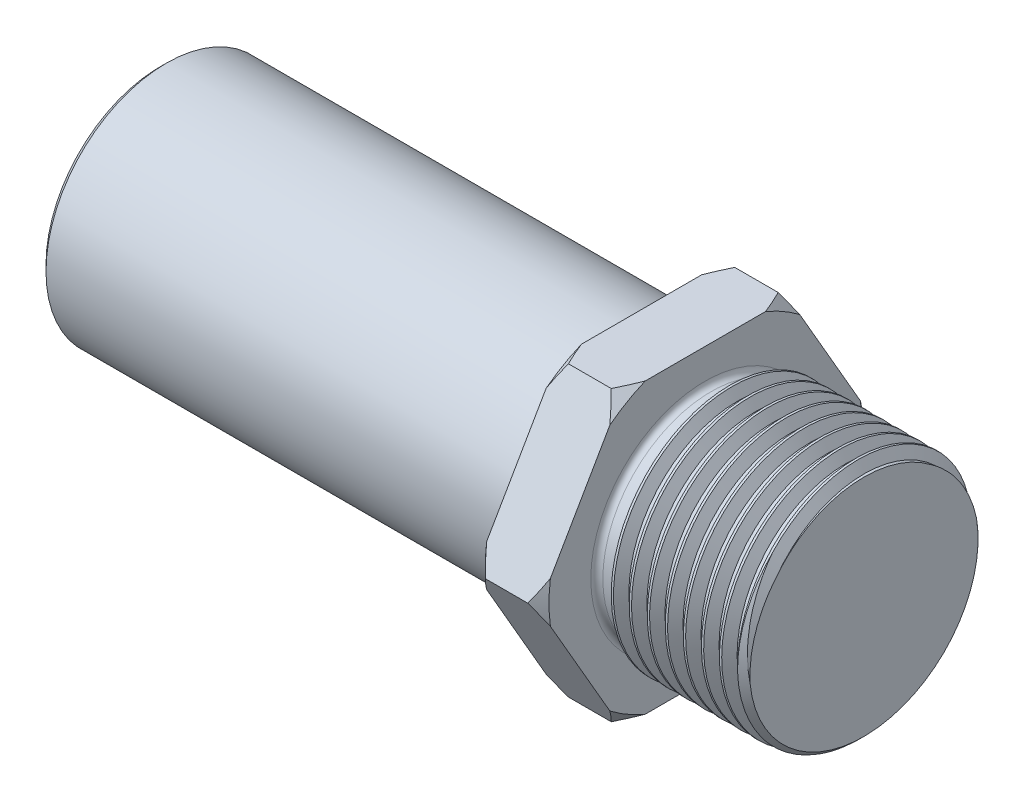
SolidWorks part; units mm, degrees
material "AISI 1045 Acero estirado en frío"
ref_plane "Alzado" through (0, 0, 0) normal (0, 0, 1) x (1, 0, 0)
ref_plane "Planta" through (0, 0, 0) normal (0, 1, 0) x (1, 0, 0)
ref_plane "Vista lateral" through (0, 0, 0) normal (1, 0, 0) x (0, 0, -1)
sketch "Croquis1" plane through (0, 0, 0) normal (0, 1, 0) x (1, 0, 0)
  line L0 (0, 0) -> (-85.2, 0) construction
  line L1 (0, 0) -> (0, 10)
  line L6 (0, 10) -> (-84.992, 10)
  line L7 (-85.2, 10) -> (-85.2, 0)
  line L8 (0, 0) -> (-85.2, 0)
  line L14 (-84.992, 10) -> (-85.2, 10)
  dimension "D3" = 20
revolve "Revolución1" add sketch "Croquis1" angle 360 about L0
sketch "Croquis2" plane through (0, 0, 0) normal (1, 0, 0) x (0, 0, -1)
  circle A1 centre (0, 0) radius 10
  circle A3 centre (0, 0) radius 10
  dimension "D1" = 0
extrude "Cortar-Extruir1" cut sketch "Croquis2" against normal blind 23
chamfer "Chaflán1" distance 0.6 angle 45 1 edges at (-85.2, 0, -10)
sketch "Croquis3" plane through (-23, 0, 0) normal (1, 0, 0) x (0, 0, -1)
  circle A1 centre (0, 0) radius 10
  circle A3 centre (0, 0) radius 10
  dimension "D1" = 0
extrude "Saliente-Extruir1" add sketch "Croquis3" along normal blind 8
sketch "Croquis4" plane through (-85.2, 0, 0) normal (-1, 0, 0) x (0, 0, 1)
  circle A0 centre (0, 0) radius 17.8458
extrude "Cortar-Extruir2" cut sketch "Croquis4" against normal blind 11.7
hole_wizard "Perforador para roscar para macho de roscar para M16x1.51" positions "Croquis5" profile "Croquis7" hole size "M16x1.5" standard "Ansi Metric"
sketch "Croquis5" plane through (-73.5, 0, 0) normal (-1, 0, 0) x (0, 0, 1)
  point P0 (0, 0)
sketch "Croquis7" plane through (-73.5, 0, 0) normal (0, 1, 0) x (0, 0, 1)
  line L0 (0, 0) -> (0, 19.3562)
  line L1 (0, 19.3562) -> (7.25, 15)
  line L2 (7.25, 15) -> (7.25, 0)
  line L5 (7.25, 0) -> (0, 0)
  line L10 (0, 19.3562) -> (-7.25, 15) construction
  line L11 (0, -6.35) -> (0, 107.95) construction
  dimension "Diámetro de taladro" = 14.5
  dimension "Profundidad de taladro" = 15
  dimension "Ángulo de perforador" = 118
thread "Rosca2" pitch 1.5 method cut profile "Perfil de rosca2" start angle 0, offset 0, length 14, pitch 1.5, diameter 14.5
ref_plane "Plano2" through (-73.5, 0, -7.25) normal (0, -1, 0) x (0, 0, -1)
sketch "Perfil de rosca2" plane through (-73.5, 0, -7.25) normal (0, -1, 0) x (0, 0, -1)
  line L0 (0, 0) -> (0, 1.5) construction
  line L1 (0, 0) -> (0.8119, 0.4687)
  line L2 (0.8119, 0.4687) -> (0.8119, 0.6562)
  line L3 (0.8119, 0.6562) -> (0, 1.125)
  line L4 (0.8119, 0.5625) -> (0, 0.5625) construction
  line L11 (0, 0) -> (0, 1.125)
  point P2 (0, 0)
  dimension "Pitch" = 1.5
  dimension "Profile_Angle" = 60
  dimension "Profile_Land" = 0.1875
  dimension "Profile_Height" = 0.8119
chamfer "Chaflán2" distance 0.5 angle 45 1 edges at (-73.5, 0, 10)
chamfer "Chaflán4" distance 0.5 angle 45 1 edges at (-15, 0, -10)
thread "Rosca3" pitch 1.5 method cut profile "Perfil de rosca3" start angle 0, offset 3, length 15, pitch 1.5, diameter 20
ref_plane "Plano3" through (-12.5, 0, 10) normal (0, -1, 0) x (0, 0, 1)
sketch "Perfil de rosca3" plane through (-12.5, 0, 10) normal (0, -1, 0) x (0, 0, 1)
  line L0 (0, 0) -> (0, 1.5) construction
  line L11 (0, 0) -> (0, 1.3125)
  line L12 (0, 1.3125) -> (-0.8119, 0.8437)
  line L13 (-0.8119, 0.8437) -> (-0.8119, 0.4687)
  line L15 (-0.8119, 0.4687) -> (0, 0)
  line L17 (-0.8119, 0.6562) -> (0, 0.6562) construction
  point P2 (0, 0)
  dimension "Pitch" = 1.5
  dimension "Profile_Angle" = 60
  dimension "Profile_Land" = 0.375
  dimension "Profile_Height" = 0.8119
sketch "Croquis8" plane through (0, 0, 0) normal (0, 1, 0) x (1, 0, 0)
  line L0 (-15, 0.0253) -> (-33.6, 0.0253) construction
  line L1 (-15, -9.4494) -> (-15, 9.5) construction
  line L6 (-28.2, -13.9747) -> (-33.5, -13.9747)
  line L7 (-28.2, -13.9747) -> (-28.2, -7.4747)
  line L8 (-28.2, -7.4747) -> (-33.5, -7.4747)
  line L9 (-33.5, -13.9747) -> (-33.5, -7.4747)
  line L10 (-28.2, -13.9747) -> (-33.5, -7.4747) construction
  line L11 (-28.2, -7.4747) -> (-33.5, -13.9747) construction
  point P4 (-30.85, -10.7247)
  dimension "D1" = 13.2
  dimension "D2" = 5.3
  dimension "D3" = 28
  dimension "D4" = 15
revolve "Revolución2" add sketch "Croquis8" angle 360 about L0
sketch "Croquis10" plane through (0, 0, 0) normal (0, 1, 0) x (1, 0, 0)
  line L0 (0, 0) -> (-82.9976, 0) construction
  line L1 (-28.2, -13.9747) -> (-28.2, 14.0253) construction
  line L2 (-28.2, -13.9747) -> (-28.2, 14.0253)
  line L4 (-28.2, -13.9747) -> (-26.7, -13.9747)
  line L5 (-26.7, -13.9747) -> (-26.7, -9)
  line L6 (-26.7, -9) -> (-28.2, -9)
  dimension "D1" = 1.5
  dimension "D2" = 18
revolve "Cortar-Revolución1" cut sketch "Croquis10" angle 360 about L0 region at (-27.45, 0, 11.4874)
fillet "Redondeo3" radius 0.5 1 edges at (-28.2, 0, -9)
chamfer "Chaflán3" distance 1 angle 45 2 edges at (-33.5, 0, -14.0253) (-28.2, 0, -14.0253)
sketch "Croquis11" plane through (-33.5, 0, 0) normal (-1, 0, 0) x (0, 0, 1)
  line L1 (13.8564, 0) -> (6.9282, 12)
  line L2 (6.9282, 12) -> (-6.9282, 12)
  line L3 (-6.9282, 12) -> (-13.8564, 0)
  line L4 (-13.8564, 0) -> (-6.9282, -12)
  line L5 (-6.9282, -12) -> (6.9282, -12)
  line L6 (6.9282, -12) -> (13.8564, 0)
  circle A0 centre (0, 0) radius 12 construction
  circle A1 centre (0, 0) radius 24.9133
  dimension "D1" = 24
extrude "Cortar-Extruir3" cut sketch "Croquis11" against normal through all both and the other way through all
fillet "Redondeo4" radius 0.5 1 edges at (-33.5, 0, -10)
